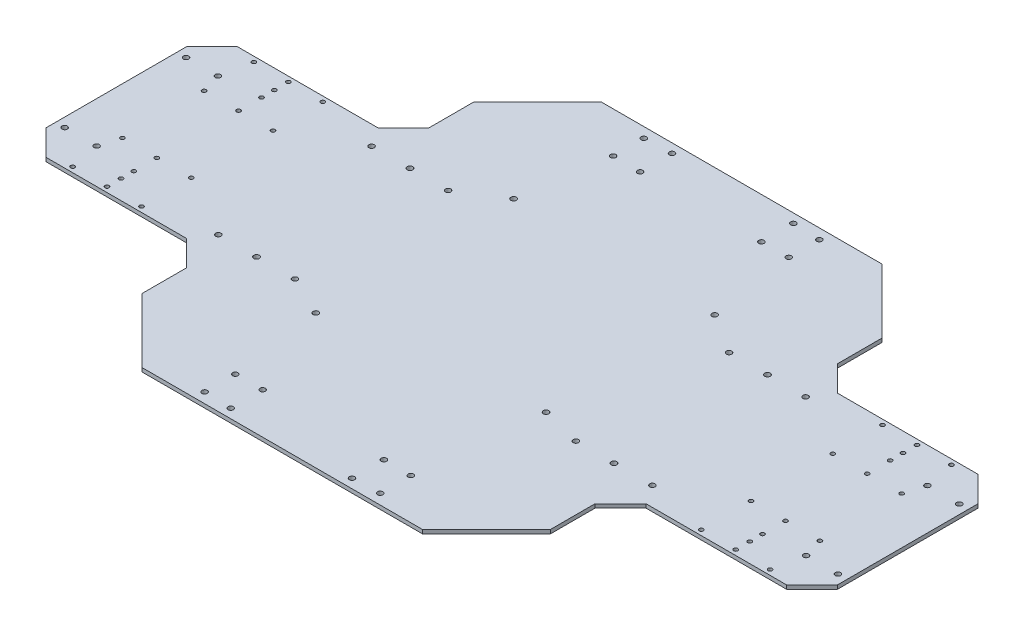
SolidWorks part; units mm, degrees
ref_plane "前视基准面" through (0, 0, 0) normal (0, 0, 1) x (1, 0, 0)
ref_plane "上视基准面" through (0, 0, 0) normal (0, 1, 0) x (1, 0, 0)
ref_plane "右视基准面" through (0, 0, 0) normal (1, 0, 0) x (0, 0, -1)
sketch "草图1" plane through (0, 0, 0) normal (0, 1, 0) x (1, 0, 0)
  line L0 (-310, 75) -> (310, -75) construction
  line L1 (-260, 200) -> (260, 200) construction
  line L2 (-260, 200) -> (-260, -200) construction
  line L3 (-260, -200) -> (260, -200) construction
  line L4 (260, 200) -> (260, -200) construction
  line L5 (310, 75) -> (-310, -75) construction
  line L6 (-160, 200) -> (160, -200) construction
  line L7 (-310, -75) -> (-160, -75)
  line L8 (-310, -75) -> (-310, 75)
  line L9 (-310, 75) -> (-160, 75)
  line L10 (310, -75) -> (310, 75)
  line L11 (160, 200) -> (-160, -200) construction
  line L13 (-160, -200) -> (160, -200)
  line L14 (-160, -200) -> (-160, -75)
  line L15 (-160, 200) -> (160, 200)
  line L16 (160, -200) -> (160, -75)
  line L19 (-160, 75) -> (-160, 200)
  line L22 (160, 75) -> (310, 75)
  line L25 (160, 75) -> (160, 200)
  line L28 (160, -75) -> (310, -75)
  point P0 (0, 0)
  point P6 (-0.5159, 0.1248)
  point P11 (0, 0)
  dimension "D1" = 520
  dimension "D2" = 400
  dimension "D3" = 50
  dimension "D4" = 125
  dimension "D5" = 100
extrude "凸台-拉伸1" add sketch "草图1" along normal blind 3
chamfer "倒角1" distance 20 angle 45 8 edges at (-160, 1.5, -75) (-310, 1.5, -75) (-310, 1.5, 75) (-160, 1.5, 75) (160, 1.5, 75) (160, 1.5, -75) (310, 1.5, 75) (310, 1.5, -75)
sketch "草图2" plane through (0, 3, 0) normal (0, 1, 0) x (1, 0, 0)
  line L0 (-160, 200) -> (-160, 95) construction
  line L1 (-160, 180) -> (160, 180)
  line L2 (-160, 180) -> (-160, 200)
  line L3 (-160, 200) -> (160, 200)
  line L4 (160, 180) -> (160, 200)
  line L6 (160, -200) -> (-160, -200)
  line L7 (160, -200) -> (160, -180)
  line L8 (160, -180) -> (-160, -180)
  line L9 (-160, -200) -> (-160, -180)
  dimension "D1" = 20
  dimension "D2" = 20
extrude "切除-拉伸1" cut sketch "草图2" against normal blind 5
chamfer "倒角2" distance 50 angle 45 4 edges at (-160, 1.5, -180) (-160, 1.5, 180) (160, 1.5, -180) (160, 1.5, 180)
sketch "草图3" plane through (0, 3, 0) normal (0, 1, 0) x (1, 0, 0)
  line L0 (0, 0) -> (144.0598, 0) construction
  line L1 (110, -180) -> (-110, -180) construction
  circle A0 centre (-302.8263, 47.5) radius 2.1
  circle A1 centre (-277.8263, 47.5) radius 2.1
  circle A2 centre (-47.5, 172.8263) radius 2.1
  circle A3 centre (-47.5, 147.8263) radius 2.1
  circle A4 centre (47.5, 172.8263) radius 2.1
  circle A5 centre (47.5, 147.8263) radius 2.1
  circle A6 centre (277.8263, 47.5) radius 2.1
  circle A7 centre (302.8263, 47.5) radius 2.1
  circle A8 centre (-68.75, 172) radius 2.1
  circle A9 centre (-68.75, 148) radius 2.1
  circle A10 centre (68.75, 172) radius 2.1
  circle A11 centre (68.75, 148) radius 2.1
  circle A12 centre (68.75, -148) radius 2.1
  circle A13 centre (68.75, -172) radius 2.1
  circle A14 centre (-68.75, -148) radius 2.1
  circle A15 centre (-68.75, -172) radius 2.1
  circle A16 centre (302.8263, -47.5) radius 2.1
  circle A17 centre (277.8263, -47.5) radius 2.1
  circle A18 centre (47.5, -147.8263) radius 2.1
  circle A19 centre (47.5, -172.8263) radius 2.1
  circle A20 centre (-47.5, -147.8263) radius 2.1
  circle A21 centre (-47.5, -172.8263) radius 2.1
  circle A22 centre (-277.8263, -47.5) radius 2.1
  circle A23 centre (-302.8263, -47.5) radius 2.1
  dimension "D1" = 4.2
  dimension "D2" = 4.2
  dimension "D3" = 4.2
  dimension "D4" = 4.2
  dimension "D5" = 4.2
  dimension "D6" = 4.2
  dimension "D7" = 4.2
  dimension "D8" = 4.2
  dimension "D9" = 180
extrude "切除-拉伸2" cut sketch "草图3" against normal blind 80
sketch "草图4" plane through (0, 0, 0) normal (0, -1, 0) x (1, 0, 0)
  circle A0 centre (-78.74, 74.91) radius 2.15
  arc A1 (-76.765, 74.91) -> (-80.715, 74.91) centre (-78.74, 74.91) ccw construction
  circle A2 centre (-78.74, -80.01) radius 2.15
  circle A3 centre (78.74, -80.01) radius 2.15
  circle A4 centre (78.74, 52.07) radius 2.15
  dimension "D1" = 4.3
  dimension "D2" = 4.3
  dimension "D3" = 4.3
  dimension "D4" = 4.3
extrude "切除-拉伸3" cut sketch "草图4" against normal blind 10
sketch "草图5" plane through (0, 3, 0) normal (0, 1, 0) x (1, 0, 0)
  line L0 (0, 0) -> (90.3311, 0) construction
  line L1 (0, 0) -> (0, 46.0052) construction
  line L3 (140, -72) -> (140, -48.2) construction
  circle A0 centre (219.2002, 71) radius 1.6
  circle A1 centre (273.2002, 71) radius 1.6
  circle A2 centre (246.2002, 71) radius 1.6
  circle A3 centre (219.2002, 31.9984) radius 1.6
  circle A4 centre (246.2002, 31.9984) radius 1.6
  circle A5 centre (273.2002, 31.9984) radius 1.6
  circle A6 centre (246.2002, 60) radius 1.6
  circle A7 centre (246.2002, 50) radius 1.6
  circle A8 centre (246.2002, -50) radius 1.6
  circle A9 centre (246.2002, -60) radius 1.6
  circle A10 centre (273.2002, -31.9984) radius 1.6
  circle A11 centre (246.2002, -31.9984) radius 1.6
  circle A12 centre (219.2002, -31.9984) radius 1.6
  circle A13 centre (246.2002, -71) radius 1.6
  circle A14 centre (273.2002, -71) radius 1.6
  circle A15 centre (219.2002, -71) radius 1.6
  circle A16 centre (-219.2002, -71) radius 1.6
  circle A17 centre (-273.2002, -71) radius 1.6
  circle A18 centre (-246.2002, -71) radius 1.6
  circle A19 centre (-219.2002, -31.9984) radius 1.6
  circle A20 centre (-246.2002, -31.9984) radius 1.6
  circle A21 centre (-273.2002, -31.9984) radius 1.6
  circle A22 centre (-246.2002, -60) radius 1.6
  circle A23 centre (-246.2002, -50) radius 1.6
  circle A24 centre (-246.2002, 50) radius 1.6
  circle A25 centre (-246.2002, 60) radius 1.6
  circle A26 centre (-273.2002, 31.9984) radius 1.6
  circle A27 centre (-246.2002, 31.9984) radius 1.6
  circle A28 centre (-219.2002, 31.9984) radius 1.6
  circle A29 centre (-246.2002, 71) radius 1.6
  circle A30 centre (-273.2002, 71) radius 1.6
  circle A31 centre (-219.2002, 71) radius 1.6
  circle A32 centre (170, -60) radius 2.1
  circle A34 centre (110, -60) radius 2.1
  circle A35 centre (140, -60.1) radius 2.2
  circle A36 centre (140, 60.1) radius 2.2
  circle A37 centre (110, 60) radius 2.1
  circle A38 centre (170, 60) radius 2.1
  circle A39 centre (-170, 60) radius 2.1
  circle A40 centre (-110, 60) radius 2.1
  circle A41 centre (-140, 60.1) radius 2.2
  circle A42 centre (-140, -60.1) radius 2.2
  circle A43 centre (-110, -60) radius 2.1
  circle A44 centre (-170, -60) radius 2.1
  dimension "D1" = 3.2
extrude "切除-拉伸4" cut sketch "草图5" against normal blind 29
